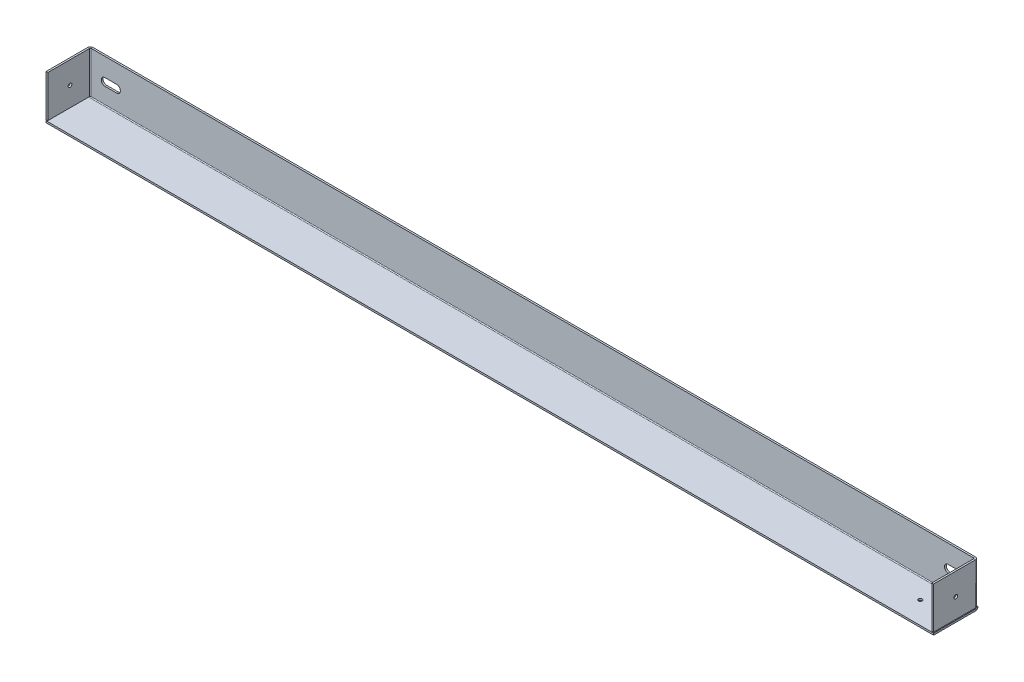
SolidWorks part; units mm, degrees
note: The reader was unsure of these and kept them because the rebuilt part matched: flange length of "Edge-Flange2", "Left Edge", "Right Edge".
ref_plane "Front Plane" through (0, 0, 0) normal (0, 0, 1) x (1, 0, 0)
ref_plane "Top Plane" through (0, 0, 0) normal (0, 1, 0) x (1, 0, 0)
ref_plane "Right Plane" through (0, 0, 0) normal (1, 0, 0) x (0, 0, -1)
sketch "BaseFlange" plane through (0, 0, 0) normal (0, 0, 1) x (1, 0, 0)
  line L1 (-500, 25) -> (500, 25)
  line L2 (-500, 25) -> (-500, -25)
  line L3 (-500, -25) -> (500, -25)
  line L4 (500, 25) -> (500, -25)
  line L5 (-500, 25) -> (500, -25) construction
  line L6 (-500, -25) -> (500, 25) construction
  point P0 (0, 0)
  dimension "Width" = 1000
  dimension "D2" = 50
base flange "BaseFlange1" sketch "BaseFlange" thickness 2 reverse thickness direction yes parameters "D1"=1
edge flange "Edge-Flange2" sketch "Sketch11" flange angle 90 flange length 50 flange position material inside bend radius 1 thickness 2 parameters "D6"=10
sketch "Sketch11" plane through (0, -25, 2) normal (0, 1, 0) x (-1, 0, 0)
  line L2 (-500, 0) -> (-500, 48)
  line L3 (-500, 48) -> (500, 48)
  line L4 (500, 48) -> (500, 0)
  line L5 (500, 0) -> (-500, 0) construction
  line L6 (500, 0) -> (-500, 0)
bend "EdgeBend2" bend radius 1 bend angle 90 parameters "D5"=1
sketch "Sketch12" plane through (0, -23, 0) normal (0, 1, 0) x (1, 0, 0)
  line L0 (500, -50) -> (500, -3) construction
  line L1 (-500, -50) -> (500, -50) construction
  circle A0 centre (460, -25) radius 2.1
  dimension "D1" = 4.2
  dimension "D3" = 25
  dimension "D2" = 40
extrude "4.2mm Hole" cut sketch "Sketch12" against normal blind 10
sketch "slot1" plane through (0, 0, 2) normal (0, 0, 1) x (1, 0, 0)
  line L0 (468.5, 0) -> (481.5, 0) construction
  line L1 (468.5, 4.25) -> (481.5, 4.25)
  line L2 (468.5, -4.25) -> (481.5, -4.25)
  line L3 (500, -22) -> (500, 25) construction
  line L4 (500, 25) -> (-500, 25) construction
  arc A0 (468.5, 4.25) -> (468.5, -4.25) centre (468.5, 0) ccw
  arc A1 (481.5, -4.25) -> (481.5, 4.25) centre (481.5, 0) ccw
  point P2 (475, 0)
  dimension "D1" = 8.5
  dimension "D2" = 13
  dimension "D3" = 25
  dimension "D4" = 25
extrude "Slot 1" cut sketch "slot1" against normal blind 10
sketch "Slots" plane through (0, 0, 2) normal (0, 0, 1) x (1, 0, 0)
  line L0 (-500, 25) -> (-500, -22) construction
  line L1 (500, 25) -> (-500, 25) construction
  point P0 (-475, 0)
  dimension "D1" = 25
  dimension "D2" = 25
pattern_sketch "Slot Pattern" of "Slot 1" driven by "Slots"
edge flange "Left Edge" sketch "Sketch21" flange angle 90 flange length 50 flange position material inside bend radius 1 thickness 2 relief none parameters "D6"=10, "D8"=1
bend "EdgeBend3" bend radius 1 bend angle 90 parameters "D5"=2
sketch "Sketch21" plane through (-500, 0, 2) normal (1, 0, 0) x (0, 1, 0)
  line L0 (25, 0) -> (-22, 0) construction
  line L1 (25, 0) -> (-22, 0)
  line L2 (25, 0) -> (25, 48)
  line L3 (25, 48) -> (-22, 48)
  line L4 (-22, 48) -> (-22, 0)
sketch "Sketch19" plane through (-500, 0, 0) normal (-1, 0, 0) x (0, 0, 1)
  line L1 (50, 25) -> (50, -22) construction
  circle A0 centre (25, 0) radius 2.1
  dimension "D1" = 4.2
  dimension "D2" = 25
extrude "Cut-Extrude1" cut sketch "Sketch19" against normal through all both normal cut yes
edge flange "Right Edge" sketch "Sketch24" flange angle 90 flange length 50 flange position material inside bend radius 1 thickness 2 relief none parameters "D6"=10
sketch "Sketch24" plane through (500, 0, 2) normal (-1, 0, 0) x (0, -1, 0)
  line L2 (-25, 0) -> (-25, 48)
  line L3 (-25, 48) -> (22, 48)
  line L4 (22, 48) -> (22, 0)
  line L5 (22, 0) -> (-25, 0) construction
  line L6 (22, 0) -> (-25, 0)
bend "EdgeBend4" bend radius 1 bend angle 90 parameters "D5"=3
sketch "Sketch25" plane through (500, 0, 0) normal (1, 0, 0) x (0, 0, -1)
  line L0 (-50, -22) -> (-50, 25) construction
  circle A0 centre (-25, 0) radius 2.1
  dimension "D1" = 4.2
  dimension "D2" = 25
extrude "Cut-Extrude2" cut sketch "Sketch25" against normal blind 10
sketch "Bend-Lines1" [suppressed] plane through (0, 0, 0) normal (0, 1, 0) x (1, 0, 0)
sketch "Bounding-Box1" [suppressed] plane through (0, 0, 0) normal (0, 1, 0) x (1, 0, 0)
sheet metal parameters "Sheet-Metal16" thickness 2 parameters "D1"=1
flat pattern "Flat-Pattern16" [suppressed]
sketch "Bend-Lines2" plane through (0, 0, 0) normal (0, 1, 0) x (1, 0, 0)
sketch3d "Bounding-Box2" [suppressed]
  line L0 (500, -25, 0) -> (-500, -25, 0) construction
  line L1 (500, 25, 0) -> (-500, 25, 0) construction
  line L2 (500, -25, 0) -> (500, 25, 0) construction
  line L3 (-500, -25, 0) -> (-500, 25, 0) construction
sheet metal parameters "Sheet-Metal18" thickness 2 parameters "D1"=1
flat pattern "Flat-Pattern16"
sketch "Bend-Lines2" plane through (0, 0, 0) normal (0, 0, -1) x (-1, 0, 0)
  line L0 (-500, -23.2017) -> (500, -23.2017) construction
  line L1 (-500, -23.2017) -> (500, -23.2017) construction
sketch3d "Bounding-Box2" [suppressed]
  line L0 (500, -71.4033, 0) -> (-500, -71.4033, 0) construction
  line L1 (500, 25, 0) -> (-500, 25, 0) construction
  line L2 (500, -71.4033, 0) -> (500, 25, 0) construction
  line L3 (-500, -71.4033, 0) -> (-500, 25, 0) construction
bend of the flat pattern "Flatten-<EdgeBend2>1"
sheet metal parameters "Sheet-Metal19" thickness 2 parameters "D1"=1
flat pattern "Flat-Pattern16"
sketch "Bend-Lines2" plane through (0, 0, 0) normal (0, 0, -1) x (-1, 0, 0)
  line L0 (-500, -23.2017) -> (500, -23.2017) construction
  line L1 (-500, -23.2017) -> (500, -23.2017) construction
sketch3d "Bounding-Box2" [suppressed]
  line L0 (500, -71.4033, 0) -> (-500, -71.4033, 0) construction
  line L1 (500, 25, 0) -> (-500, 25, 0) construction
  line L2 (500, -71.4033, 0) -> (500, 25, 0) construction
  line L3 (-500, -71.4033, 0) -> (-500, 25, 0) construction
bend of the flat pattern "Flatten-<EdgeBend2>1"
sheet metal parameters "Sheet-Metal20" thickness 2 parameters "D1"=1
flat pattern "Flat-Pattern16"
sketch "Bend-Lines2" plane through (0, 0, 0) normal (0, 0, -1) x (-1, 0, 0)
  line L0 (-500, -23.2017) -> (500, -23.2017) construction
  line L1 (-500, -23.2017) -> (500, -23.2017) construction
sketch3d "Bounding-Box2" [suppressed]
  line L0 (500, -71.4033, 0) -> (-500, -71.4033, 0) construction
  line L1 (500, 25, 0) -> (-500, 25, 0) construction
  line L2 (500, -71.4033, 0) -> (500, 25, 0) construction
  line L3 (-500, -71.4033, 0) -> (-500, 25, 0) construction
bend of the flat pattern "Flatten-<EdgeBend2>1"
sheet metal parameters "Sheet-Metal21" thickness 2 parameters "D1"=1
flat pattern "Flat-Pattern16"
sketch "Bend-Lines2" plane through (0, 0, 0) normal (0, 0, -1) x (-1, 0, 0)
  line L0 (-500, -23.2017) -> (500, -23.2017) construction
  line L1 (-500, -23.2017) -> (500, -23.2017) construction
sketch3d "Bounding-Box2" [suppressed]
  line L0 (500, -71.4033, 0) -> (-500, -71.4033, 0) construction
  line L1 (500, 25, 0) -> (-500, 25, 0) construction
  line L2 (500, -71.4033, 0) -> (500, 25, 0) construction
  line L3 (-500, -71.4033, 0) -> (-500, 25, 0) construction
bend of the flat pattern "Flatten-<EdgeBend2>1"
sheet metal parameters "Sheet-Metal22" thickness 2 parameters "D1"=1
flat pattern "Flat-Pattern16" [suppressed]
sketch "Bend-Lines2" plane through (0, 0, 0) normal (0, 0, -1) x (-1, 0, 0)
  line L0 (-500, -23.2017) -> (500, -23.2017) construction
  line L1 (-500, -23.2017) -> (500, -23.2017) construction
  line L2 (498.2017, -22) -> (498.2017, 25) construction
  line L3 (-498.2017, 25) -> (-498.2017, -22) construction
  line L4 (498.2017, -22) -> (498.2017, 25) construction
  line L5 (-498.2017, 25) -> (-498.2017, -22) construction
sketch3d "Bounding-Box2" [suppressed]
  line L0 (546.4033, -71.4033, 0) -> (-546.4033, -71.4033, 0) construction
  line L1 (546.4033, 25, 0) -> (-546.4033, 25, 0) construction
  line L2 (546.4033, -71.4033, 0) -> (546.4033, 25, 0) construction
  line L3 (-546.4033, -71.4033, 0) -> (-546.4033, 25, 0) construction
bend of the flat pattern "Flatten-<EdgeBend2>1"
bend of the flat pattern "Flatten-<EdgeBend3>1"
sheet metal parameters "Sheet-Metal23" thickness 2 parameters "D1"=1
flat pattern "Flat-Pattern16"
sketch "Bend-Lines2" plane through (0, 0, 0) normal (0, 0, -1) x (-1, 0, 0)
  line L0 (-500, -23.2017) -> (500, -23.2017) construction
  line L1 (-500, -23.2017) -> (500, -23.2017) construction
  line L2 (498.2017, -22) -> (498.2017, 25) construction
  line L4 (498.2017, -22) -> (498.2017, 25) construction
sketch3d "Bounding-Box2" [suppressed]
  line L0 (546.4033, -71.4033, 0) -> (-500, -71.4033, 0) construction
  line L1 (546.4033, 25, 0) -> (-500, 25, 0) construction
  line L2 (546.4033, -71.4033, 0) -> (546.4033, 25, 0) construction
  line L3 (-500, -71.4033, 0) -> (-500, 25, 0) construction
bend of the flat pattern "Flatten-<EdgeBend2>1"
bend of the flat pattern "Flatten-<EdgeBend3>2"
sheet metal parameters "Sheet-Metal24" thickness 2 parameters "D1"=1
flat pattern "Flat-Pattern16"
sketch "Bend-Lines2" plane through (0, 0, 0) normal (0, 0, -1) x (-1, 0, 0)
  line L0 (-500, -23.2017) -> (500, -23.2017) construction
  line L1 (-500, -23.2017) -> (500, -23.2017) construction
  line L2 (498.2017, -22) -> (498.2017, 25) construction
  line L3 (-498.2017, 25) -> (-498.2017, -22) construction
  line L4 (498.2017, -22) -> (498.2017, 25) construction
  line L5 (-498.2017, 25) -> (-498.2017, -22) construction
sketch3d "Bounding-Box2" [suppressed]
  line L0 (546.4033, -71.4033, 0) -> (-546.4033, -71.4033, 0) construction
  line L1 (546.4033, 25, 0) -> (-546.4033, 25, 0) construction
  line L2 (546.4033, -71.4033, 0) -> (546.4033, 25, 0) construction
  line L3 (-546.4033, -71.4033, 0) -> (-546.4033, 25, 0) construction
bend of the flat pattern "Flatten-<EdgeBend2>1"
bend of the flat pattern "Flatten-<EdgeBend3>2"
bend of the flat pattern "Flatten-<EdgeBend4>1"
sheet metal parameters "Sheet-Metal25" thickness 2 parameters "D1"=1
flat pattern "Flat-Pattern16"
sketch "Bend-Lines2" plane through (0, 0, 0) normal (0, 0, -1) x (-1, 0, 0)
  line L0 (-500, -23.2017) -> (500, -23.2017) construction
  line L1 (-500, -23.2017) -> (500, -23.2017) construction
  line L2 (498.2017, -22) -> (498.2017, 25) construction
  line L3 (-498.2017, 25) -> (-498.2017, -22) construction
  line L4 (498.2017, -22) -> (498.2017, 25) construction
  line L5 (-498.2017, 25) -> (-498.2017, -22) construction
sketch3d "Bounding-Box2" [suppressed]
  line L0 (546.4033, -71.4033, 0) -> (-546.4033, -71.4033, 0) construction
  line L1 (546.4033, 25, 0) -> (-546.4033, 25, 0) construction
  line L2 (546.4033, -71.4033, 0) -> (546.4033, 25, 0) construction
  line L3 (-546.4033, -71.4033, 0) -> (-546.4033, 25, 0) construction
bend of the flat pattern "Flatten-<EdgeBend2>1"
bend of the flat pattern "Flatten-<EdgeBend3>2"
bend of the flat pattern "Flatten-<EdgeBend4>1"
